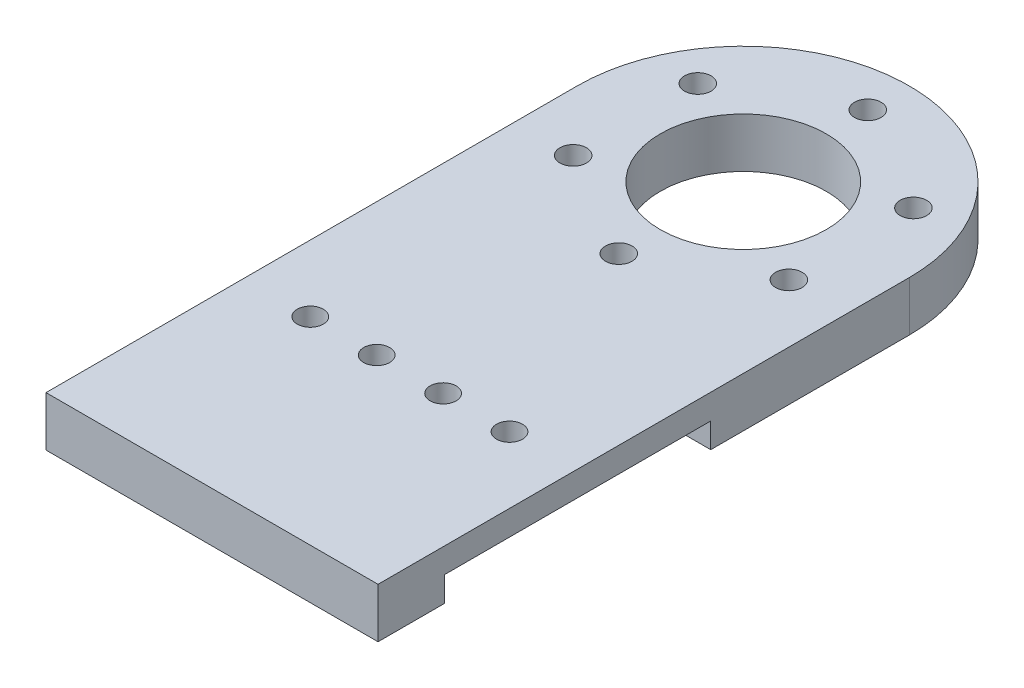
SolidWorks part; units mm, degrees
ref_plane "Front Plane" through (0, 0, 0) normal (0, 0, 1) x (1, 0, 0)
ref_plane "Top Plane" through (0, 0, 0) normal (0, 1, 0) x (1, 0, 0)
ref_plane "Right Plane" through (0, 0, 0) normal (1, 0, 0) x (0, 0, -1)
sketch "Sketch1" plane through (0, 0, 0) normal (0, 1, 0) x (1, 0, 0)
  line L0 (0, -111.3091) -> (63.5, -111.3091)
  line L2 (0, -22.4091) -> (0, -124.0091)
  line L3 (0, -124.0091) -> (63.5, -124.0091)
  line L4 (63.5, -22.4091) -> (63.5, -124.0091)
  line L7 (0, -60.3821) -> (63.5, -60.3821)
  circle A0 centre (31.75, -22.4091) radius 15.875
  circle A1 centre (12.7, -86.1631) radius 2.4892
  circle A2 centre (25.4, -86.1631) radius 2.4892
  circle A3 centre (38.1, -86.1631) radius 2.4892
  circle A4 centre (50.8, -86.1631) radius 2.4892
  arc A5 (63.5, -22.4091) -> (0, -22.4091) centre (31.75, -22.4091) ccw
  dimension "D3" = 31.75
  dimension "D5" = 31.75
  dimension "D6" = 4.9784
  dimension "D7" = 12.7
  dimension "D8" = 37.846
  dimension "D10" = 12.7
  dimension "D12" = 63.627
  dimension "D9" = 4
extrude "Boss-Extrude2" add sketch "Sketch1" along normal blind 9.525 contours L4 L0 L2 L3 | L2 L7 L4 A0 | A5 | A5 L2 L3 L4 | A0 | A4 | A3 | A2 | A1 region at (31.75, 0, 117.6591) region at (0.9431, 0, 41.3956)
extrude "Boss-Extrude3" add sketch "Sketch1<3>" along normal blind 3.175 contours L7 L2 L0 L4 A4 A3 A2 A1 region at (31.75, 0, 85.8377)
sketch "Sketch1<3>" plane through (0, 0, 0) normal (0, 1, 0) x (1, 0, 0) same geometry as "Sketch1"
sketch "Sketch2" plane through (0, 0, 0) normal (0, -1, 0) x (1, 0, 0)
  line L0 (11.1252, 34.3109) -> (52.3748, 34.3109) construction
  line L1 (31.75, 38.2841) -> (31.75, 6.5341) construction
  line L2 (15.875, 22.4091) -> (47.625, 22.4091) construction
  circle A4 centre (31.75, 22.4091) radius 15.875 construction
  circle A5 centre (31.75, 22.4091) radius 23.8125 construction
  circle A6 centre (11.1252, 34.3109) radius 2.54
  circle A7 centre (52.3748, 34.3109) radius 2.54
  circle A8 centre (11.1377, 10.4857) radius 2.54
  circle A9 centre (52.3623, 10.4857) radius 2.54
  circle A10 centre (31.75, 46.2216) radius 2.54
  circle A11 centre (31.75, -1.4034) radius 2.54
  dimension "D1" = 5.08
  dimension "D3" = 47.625
  dimension "D2" = 41.2496
  dimension "D4" = 5.08
  dimension "D5" = 5.08
  dimension "D6" = 5.08
  dimension "D9" = 5.08
  dimension "D7" = 23.8252
  dimension "D8" = 23.8252
extrude "Cut-Extrude1" cut sketch "Sketch2" against normal through all contours A10 | A11 | A9 | A8 | A7 | A6 region at (31.75, 0, 46.2216) region at (31.75, 0, -1.4034)
extrude "Cut-Extrude7" cut sketch "Sketch1<7>" along normal blind 4.7625 contours L7 L2 L0 L4 A4 A3 A2 A1 region at (31.75, 0, 85.8377)
sketch "Sketch1<7>" plane through (0, 0, 0) normal (0, 1, 0) x (1, 0, 0) same geometry as "Sketch1"
